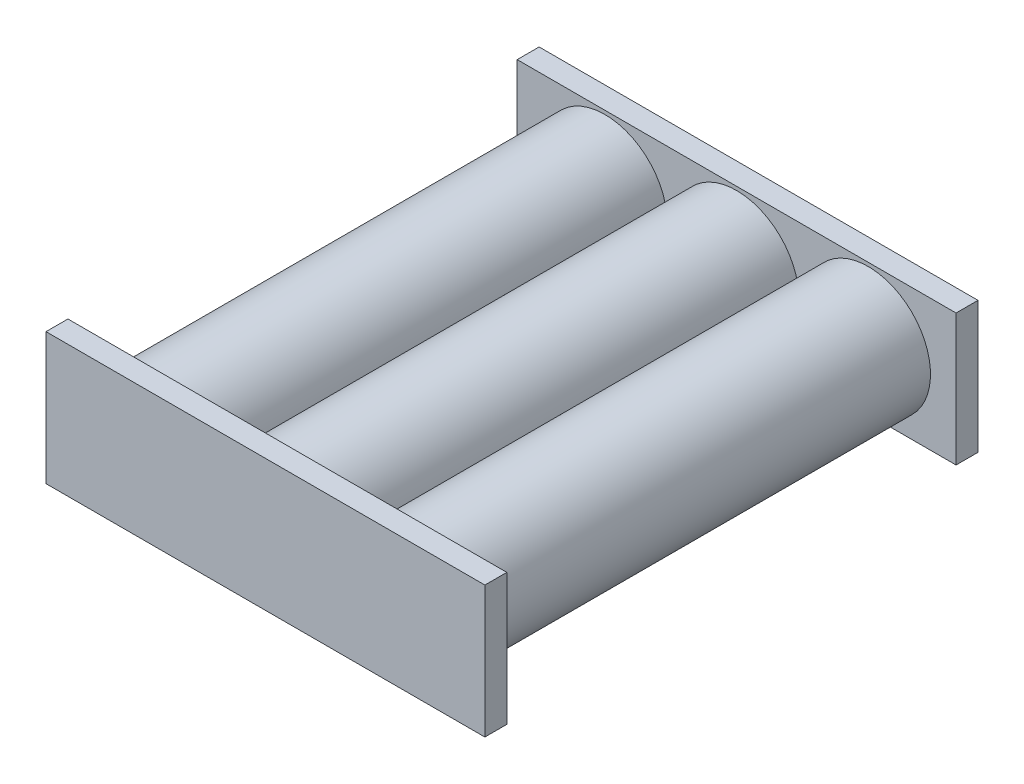
SolidWorks part; units mm, degrees
ref_plane "Front Plane" through (0, 0, 0) normal (0, 0, 1) x (1, 0, 0)
ref_plane "Top Plane" through (0, 0, 0) normal (0, 1, 0) x (1, 0, 0)
ref_plane "Right Plane" through (0, 0, 0) normal (1, 0, 0) x (0, 0, -1)
sketch "Sketch1" plane through (0, 0, 0) normal (0, 0, 1) x (1, 0, 0)
  circle A0 centre (0, 0) radius 9
  dimension "D1" = 18
extrude "Boss-Extrude1" add sketch "Sketch1" along normal blind 65
ref_axis "Axis1" through (-9.9, 0, 0) along (1, 0, 0)
pattern_linear "LPattern1" count 3 spacing 19.05 along (1, 0, 0) of "Boss-Extrude1"
sketch "Sketch2" plane through (0, 0, 0) normal (0, 0, -1) x (-1, 0, 0)
  line L1 (-50.8, 9.525) -> (12.7, 9.525)
  line L2 (-50.8, 9.525) -> (-50.8, -9.525)
  line L3 (-50.8, -9.525) -> (12.7, -9.525)
  line L4 (12.7, 9.525) -> (12.7, -9.525)
  circle A0 centre (-38.1, 0) radius 9 construction
  point P6 (-19.05, 9.525)
  point P10 (-19.05, 0)
  dimension "D1" = 9.525
  dimension "D2" = 19.05
  dimension "D3" = 63.5
extrude "Boss-Extrude5" add sketch "Sketch2" along normal blind 3.175 contours L1 L4 L3 L2
pattern_linear "LPattern2" count 2 spacing 68.175 along (0, 0, 1) of "Boss-Extrude5"
